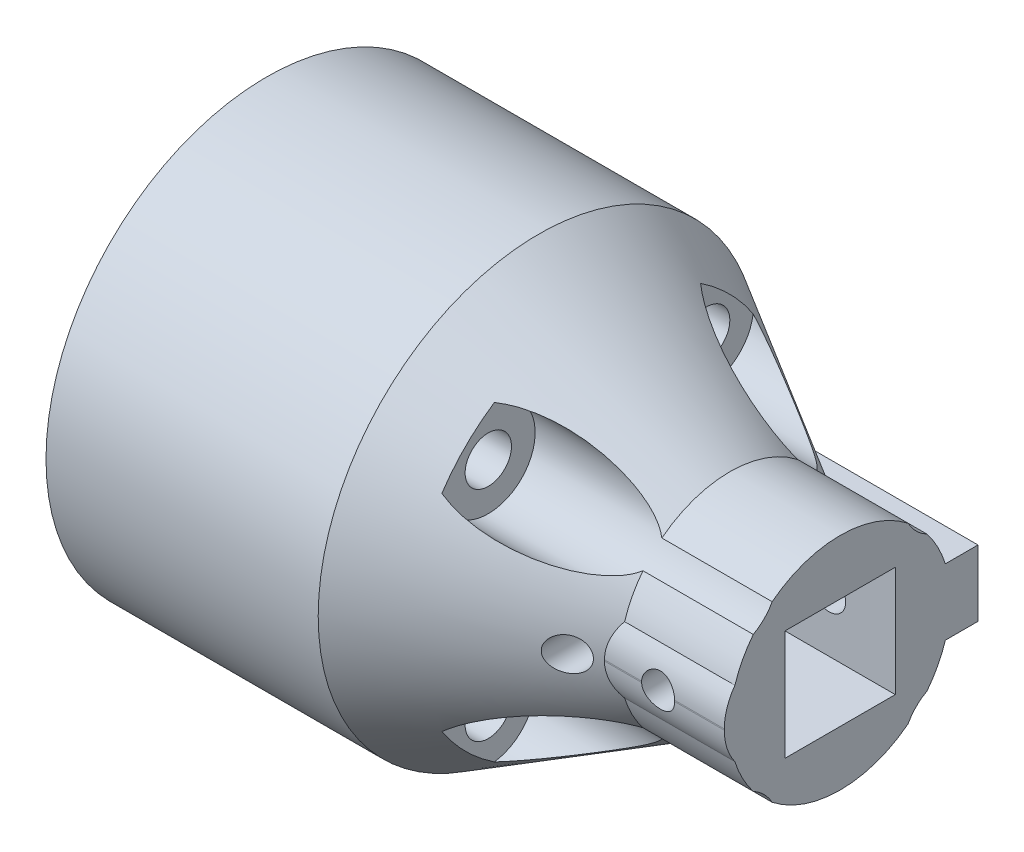
SolidWorks part; units mm, degrees
ref_plane "前视基准面" through (0, 0, 0) normal (0, 0, 1) x (1, 0, 0)
ref_plane "上视基准面" through (0, 0, 0) normal (0, 1, 0) x (1, 0, 0)
ref_plane "右视基准面" through (0, 0, 0) normal (1, 0, 0) x (0, 0, -1)
sketch "草图1" plane through (0, 0, 0) normal (1, 0, 0) x (0, 0, -1)
  circle A0 centre (0, 0) radius 20
  dimension "D1" = 40
extrude "凸台-拉伸1" add sketch "草图1" along normal blind 5
sketch "草图2" plane through (5, 0, 0) normal (1, 0, 0) x (0, 0, -1)
  line L1 (-3.15, -3.15) -> (3.15, -3.15)
  line L2 (-3.15, -3.15) -> (-3.15, 3.15)
  line L3 (-3.15, 3.15) -> (3.15, 3.15)
  line L4 (3.15, -3.15) -> (3.15, 3.15)
  line L5 (-3.15, -3.15) -> (3.15, 3.15) construction
  line L6 (-3.15, 3.15) -> (3.15, -3.15) construction
  point P0 (0, 0)
  dimension "D1" = 6.3
  dimension "D2" = 6.3
extrude "切除-拉伸1" cut sketch "草图2" against normal blind 5
sketch "草图4" plane through (0, 0, 0) normal (-1, 0, 0) x (0, 0, 1)
  circle A0 centre (0, 0) radius 20
  circle A1 centre (0, 0) radius 10
  dimension "D1" = 20
extrude "凸台-拉伸2" add sketch "草图4" along normal blind 7
sketch "草图3" plane through (0, 0, 0) normal (-1, 0, 0) x (0, 0, 1)
  line L0 (0, 0) -> (20, 0) construction
  line L1 (0, 0) -> (21.8171, -21.8171) construction
  circle A0 centre (0, 0) radius 14 construction
  circle A3 centre (9.8995, -9.8995) radius 2.1
  circle A4 centre (0, 0) radius 14 construction
  circle A5 centre (-9.8995, -9.8995) radius 2.1
  circle A6 centre (0, 0) radius 14 construction
  circle A7 centre (-9.8995, 9.8995) radius 2.1
  circle A8 centre (0, 0) radius 14 construction
  circle A9 centre (9.8995, 9.8995) radius 2.1
  point P22 (0, 0)
  dimension "D1" = 28
  dimension "D2" = 4.2
  dimension "D3" = 45
  dimension "D4" = 4
extrude "切除-拉伸2" cut sketch "草图3" against normal blind 20 and the other way blind 20
sketch "草图5" plane through (5, 0, 0) normal (1, 0, 0) x (0, 0, -1)
  line L1 (15.5, -3) -> (12.5, -3)
  line L2 (15.5, -3) -> (15.5, 3)
  line L3 (15.5, 3) -> (12.5, 3)
  line L4 (12.5, -3) -> (12.5, 3)
  line L5 (15.5, -3) -> (12.5, 3) construction
  line L6 (15.5, 3) -> (12.5, -3) construction
  point P0 (14, 0)
  dimension "D1" = 14
  dimension "D2" = 3
  dimension "D3" = 6
extrude "切除-拉伸3" cut sketch "草图5" against normal blind 13
chamfer "倒角1" distance 1 angle 45 4 edges at (-7, 3, -14) (-7, 0, -15.5) (-7, -3, -14) (-7, 0, -12.5)
sketch "草图6" plane through (-7, 0, 0) normal (-1, 0, 0) x (0, 0, 1)
  circle A0 centre (0, 0) radius 20
  circle A1 centre (0, 0) radius 18
  dimension "D1" = 40
  dimension "D2" = 36
extrude "凸台-拉伸3" add sketch "草图6" along normal blind 20
chamfer "倒角2" distance 1 angle 45 1 edges at (-27, 0, 18)
sketch "草图7" plane through (5, 0, 0) normal (1, 0, 0) x (0, 0, -1)
  circle A0 centre (-9.8995, 9.8995) radius 4.25
  circle A1 centre (9.8995, 9.8995) radius 4.25
  circle A2 centre (9.8995, -9.8995) radius 4.25
  circle A3 centre (-9.8995, -9.8995) radius 4.25
  point P12 (0, 0)
  dimension "D1" = 8.5
  dimension "D2" = 4
extrude "切除-拉伸4" cut sketch "草图7" against normal blind 2
sketch "草图8" plane through (5, 0, 0) normal (1, 0, 0) x (0, 0, -1)
  line L1 (7, -7) -> (-7, -7)
  line L2 (7, -7) -> (7, 7)
  line L3 (7, 7) -> (-7, 7)
  line L4 (-7, -7) -> (-7, 7)
  line L5 (7, -7) -> (-7, 7) construction
  line L6 (7, 7) -> (-7, -7) construction
  point P0 (0, 0)
  dimension "D1" = 14
  dimension "D2" = 14
extrude "凸台-拉伸4" [suppressed] add sketch "草图8" along normal blind 3
sketch "草图9" [suppressed] plane through (5, 0, 0) normal (-1, 0, 0) x (0, 0, 1)
  line L1 (-3.15, -3.15) -> (3.15, -3.15)
  line L2 (-3.15, -3.15) -> (-3.15, 3.15)
  line L3 (-3.15, 3.15) -> (3.15, 3.15)
  line L4 (3.15, -3.15) -> (3.15, 3.15)
  line L5 (-3.15, -3.15) -> (3.15, 3.15) construction
  line L6 (-3.15, 3.15) -> (3.15, -3.15) construction
  point P0 (0, 0)
  dimension "D1" = 6.3
extrude "切除-拉伸5" [suppressed] cut sketch "草图9" against normal blind 10
sketch "草图10" [suppressed] plane through (0, 0, -7) normal (0, 0, -1) x (-1, 0, 0)
  line L0 (-5, -6.7922) -> (-5, 6.7922) construction
  line L1 (-3.5, -2.5) -> (-6.5, -2.5)
  line L2 (-3.5, -2.5) -> (-3.5, 2.5)
  line L3 (-3.5, 2.5) -> (-6.5, 2.5)
  line L4 (-6.5, -2.5) -> (-6.5, 2.5)
  line L5 (-3.5, -2.5) -> (-6.5, 2.5) construction
  line L6 (-3.5, 2.5) -> (-6.5, -2.5) construction
  point P0 (-5, 0)
  dimension "D1" = 3
  dimension "D2" = 5
extrude "切除-拉伸6" [suppressed] cut sketch "草图10" against normal blind 5 and the other way blind 6
fillet "圆角1" [suppressed] radius 4
fillet "圆角2" [suppressed] radius 2
sketch "草图11" [suppressed] plane through (8, 0, 0) normal (1, 0, 0) x (0, 0, -1)
  line L1 (6.35, -6.35) -> (-6.35, -6.35)
  line L2 (6.35, -6.35) -> (6.35, 6.35)
  line L3 (6.35, 6.35) -> (-6.35, 6.35)
  line L4 (-6.35, -6.35) -> (-6.35, 6.35)
  line L5 (6.35, -6.35) -> (-6.35, 6.35) construction
  line L6 (6.35, 6.35) -> (-6.35, -6.35) construction
  line L8 (-3.15, -3.15) -> (3.15, -3.15)
  line L9 (-3.15, -3.15) -> (-3.15, 3.15)
  line L10 (-3.15, 3.15) -> (3.15, 3.15)
  line L11 (3.15, -3.15) -> (3.15, 3.15)
  line L12 (-3.15, -3.15) -> (3.15, 3.15) construction
  line L13 (-3.15, 3.15) -> (3.15, -3.15) construction
  point P0 (0, 0)
  point P6 (0, 0)
  dimension "D1" = 12.7
  dimension "D2" = 12.7
extrude "凸台-拉伸5" [suppressed] add sketch "草图11" along normal blind 20
chamfer "倒角3" [suppressed] distance 2.5 angle 45
sketch "草图12" [suppressed] plane through (0, -6.35, 0) normal (0, -1, 0) x (1, 0, 0)
  line L0 (8, 6.35) -> (8, -6.35) construction
  circle A0 centre (18, 0) radius 1.65
  dimension "D1" = 3.3
  dimension "D2" = 10
extrude "切除-拉伸7" [suppressed] cut sketch "草图12" against normal blind 20
fillet "圆角3" [suppressed] radius 2.5
sketch "草图13" plane through (5, 0, 0) normal (1, 0, 0) x (0, 0, -1)
  circle A0 centre (-9.8995, 9.8995) radius 4.25 construction
  circle A1 centre (0, 0) radius 20
  circle A2 centre (0, 0) radius 20
  circle A3 centre (-9.8995, 9.8995) radius 4.25
  circle A4 centre (9.8995, 9.8995) radius 4.25 construction
  circle A5 centre (9.8995, 9.8995) radius 4.25
  circle A6 centre (-9.8995, -9.8995) radius 4.25 construction
  circle A7 centre (-9.8995, -9.8995) radius 4.25
  circle A8 centre (9.8995, -9.8995) radius 4.25 construction
  circle A9 centre (9.8995, -9.8995) radius 4.25
  dimension "D1" = 0
extrude "凸台-拉伸6" add sketch "草图13" along normal blind 10
sketch "草图14" plane through (15, 0, 0) normal (1, 0, 0) x (0, 0, -1)
  line L1 (5, -5) -> (-5, -5)
  line L2 (5, -5) -> (5, 5)
  line L3 (5, 5) -> (-5, 5)
  line L4 (-5, -5) -> (-5, 5)
  line L5 (5, -5) -> (-5, 5) construction
  line L6 (5, 5) -> (-5, -5) construction
  point P0 (0, 0)
  dimension "D1" = 10
  dimension "D2" = 10
extrude "切除-拉伸8" cut sketch "草图14" against normal blind 10
chamfer "倒角4" distance 1 angle 45 4 edges at (5, -3.15, 0) (5, 0, 3.15) (5, 3.15, 0) (5, 0, -3.15)
chamfer "倒角5" distance 0.85 angle 45 4 edges at (5, 0, 5) (5, -5, 0) (5, 0, -5) (5, 5, 0)
sketch "草图15" plane through (5, 0, 0) normal (-1, 0, 0) x (0, 0, 1)
  line L4 (-12.5, -3) -> (-12.5, 3)
  line L5 (-12.5, 3) -> (-15.5, 3)
  line L6 (-15.5, 3) -> (-15.5, -3)
  line L7 (-15.5, -3) -> (-12.5, -3)
  line L8 (-12.5, -3) -> (-12.5, 3)
  line L9 (-12.5, 3) -> (-15.5, 3)
  line L10 (-15.5, 3) -> (-15.5, -3)
  line L11 (-15.5, -3) -> (-12.5, -3)
  dimension "D1" = 0
extrude "切除-拉伸9" cut sketch "草图15" against normal blind 10
fillet "圆角4" [suppressed] radius 10
chamfer "倒角6" distance 10 angle 60 1 edges at (15, 0, -20) first distance on face at (15, 0, -14)
sketch "草图16" plane through (15, 0, 0) normal (1, 0, 0) x (0, 0, -1)
  line L1 (-5, -5) -> (5, -5)
  line L2 (-5, -5) -> (-5, 5)
  line L3 (-5, 5) -> (5, 5)
  line L4 (5, -5) -> (5, 5)
  line L5 (-5, -5) -> (5, 5) construction
  line L6 (-5, 5) -> (5, -5) construction
  arc A8 (-7.8757, 6.1623) -> (-6.1623, 7.8757) centre (-9.8995, 9.8995) ccw
  arc A9 (-7.8757, 6.1623) -> (-7.8757, -6.1623) centre (0, 0) ccw
  arc A10 (-6.1623, -7.8757) -> (-7.8757, -6.1623) centre (-9.8995, -9.8995) ccw
  arc A11 (-6.1623, -7.8757) -> (6.1623, -7.8757) centre (0, 0) ccw
  arc A12 (7.8757, -6.1623) -> (6.1623, -7.8757) centre (9.8995, -9.8995) ccw
  arc A13 (7.8757, -6.1623) -> (7.8757, 6.1623) centre (0, 0) ccw
  arc A14 (6.1623, 7.8757) -> (7.8757, 6.1623) centre (9.8995, 9.8995) ccw
  arc A15 (6.1623, 7.8757) -> (-6.1623, 7.8757) centre (0, 0) ccw
  arc A16 (-7.8757, 6.1623) -> (-6.1623, 7.8757) centre (-9.8995, 9.8995) ccw
  arc A17 (-7.8757, 6.1623) -> (-7.8757, -6.1623) centre (0, 0) ccw
  arc A18 (-6.1623, -7.8757) -> (-7.8757, -6.1623) centre (-9.8995, -9.8995) ccw
  arc A19 (-6.1623, -7.8757) -> (6.1623, -7.8757) centre (0, 0) ccw
  arc A20 (7.8757, -6.1623) -> (6.1623, -7.8757) centre (9.8995, -9.8995) ccw
  arc A21 (7.8757, -6.1623) -> (7.8757, 6.1623) centre (0, 0) ccw
  arc A22 (6.1623, 7.8757) -> (7.8757, 6.1623) centre (9.8995, 9.8995) ccw
  arc A23 (6.1623, 7.8757) -> (-6.1623, 7.8757) centre (0, 0) ccw
  dimension "D1" = 0
extrude "凸台-拉伸7" add sketch "草图16" along normal blind 10
sketch "草图18" plane through (25, 0, 0) normal (1, 0, 0) x (0, 0, -1)
  line L1 (-9.5, -3) -> (-10.5, -3)
  line L2 (-9.5, -3) -> (-9.5, 3)
  line L3 (-9.5, 3) -> (-10.5, 3)
  line L4 (-10.5, -3) -> (-10.5, 3)
  line L5 (-9.5, -3) -> (-10.5, 3) construction
  line L6 (-9.5, 3) -> (-10.5, -3) construction
  line L7 (7.5, 3) -> (12.5, 3)
  line L8 (7.5, 3) -> (7.5, -3)
  line L9 (7.5, -3) -> (12.5, -3)
  line L10 (12.5, 3) -> (12.5, -3)
  line L11 (7.5, 3) -> (12.5, -3) construction
  line L12 (7.5, -3) -> (12.5, 3) construction
  arc A0 (-7.8757, 6.1623) -> (-7.8757, -6.1623) centre (0, 0) ccw construction
  arc A1 (7.8757, -6.1623) -> (7.8757, 6.1623) centre (0, 0) ccw construction
  point P0 (-10, 0)
  point P8 (10, 0)
  dimension "D1" = 6
  dimension "D2" = 5
  dimension "D3" = 6
  dimension "D4" = 1
extrude "凸台-拉伸8" add sketch "草图18" against normal blind 17
sketch "草图17" plane through (0, 0, 5) normal (0, 0, -1) x (-1, 0, 0)
  line L0 (-25, -3) -> (-25, -6.1623) construction
  line L1 (-5.85, -5) -> (-25, -5) construction
  circle A0 centre (-12, 0) radius 1.5
  circle A1 centre (-19, 0) radius 1.5
  dimension "D1" = 3
  dimension "D2" = 13
  dimension "D3" = 3
  dimension "D4" = 6
  dimension "D5" = 5
extrude "切除-拉伸10" cut sketch "草图17" along normal blind 30 and the other way blind 10
fillet "圆角5" radius 5 2 edges at (19.2031, 3, 10.5) (19.2031, -3, 10.5)
